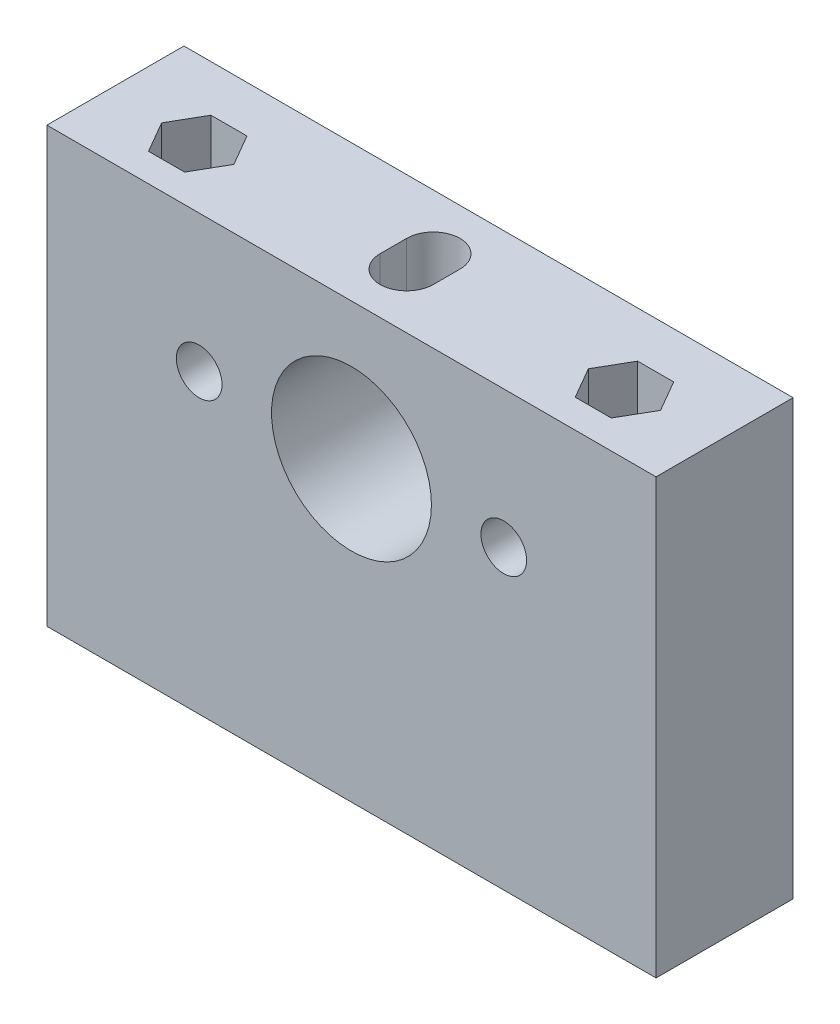
SolidWorks part; units mm, degrees
ref_plane "Front Plane" through (0, 0, 0) normal (0, 0, 1) x (1, 0, 0)
ref_plane "Top Plane" through (0, 0, 0) normal (0, 1, 0) x (1, 0, 0)
ref_plane "Right Plane" through (0, 0, 0) normal (1, 0, 0) x (0, 0, -1)
sketch "Sketch1" plane through (0, 0, 0) normal (0, 1, 0) x (1, 0, 0)
  line L0 (147.5033, 0) -> (147.5033, -18)
  line L1 (0, 0) -> (215, 0)
  line L2 (0, 0) -> (0, -18)
  line L3 (0, -18) -> (215, -18)
  line L4 (215, 0) -> (215, -18)
  line L5 (67.5033, 0) -> (67.5033, -18)
  line L6 (104.0033, -10.75) -> (104.0033, -7.25)
  line L7 (111.0033, -10.75) -> (111.0033, -7.25)
  line L8 (95.0033, -18) -> (95.0033, 0)
  line L9 (120.0033, -18) -> (120.0033, 0)
  line L10 (137.8704, -6.05) -> (133.1362, -6.05)
  line L11 (133.1362, -6.05) -> (130.769, -10.15)
  line L12 (130.769, -10.15) -> (133.1362, -14.25)
  line L13 (133.1362, -14.25) -> (137.8704, -14.25)
  line L14 (137.8704, -14.25) -> (140.2376, -10.15)
  line L15 (140.2376, -10.15) -> (137.8704, -6.05)
  line L16 (137.8704, -6.05) -> (133.1362, -14.25) construction
  line L17 (133.1362, -6.05) -> (137.8704, -14.25) construction
  line L18 (107.5, 0) -> (107.5033, -3.75) construction
  line L19 (77.1547, -14.3034) -> (74.7803, -10.2076)
  line L20 (81.889, -14.2951) -> (77.1547, -14.3034)
  line L21 (84.2489, -10.1909) -> (81.889, -14.2951)
  line L22 (81.8745, -6.0951) -> (84.2489, -10.1909)
  line L23 (74.7803, -10.2076) -> (77.1403, -6.1034)
  line L24 (77.1403, -6.1034) -> (81.889, -14.2951) construction
  line L25 (81.8745, -6.0951) -> (77.1547, -14.3034) construction
  line L26 (77.1403, -6.1034) -> (81.8745, -6.0951)
  circle A0 centre (9.99, -11.15) radius 3
  circle A1 centre (41.99, -11.15) radius 3
  circle A2 centre (79.5033, -10.15) radius 3
  circle A3 centre (135.5033, -10.15) radius 3
  circle A4 centre (173.0133, -11.15) radius 3
  circle A5 centre (205.0133, -11.15) radius 3
  circle A6 centre (107.5033, -10.75) radius 3.5
  circle A7 centre (107.5033, -7.25) radius 3.5
  point P39 (135.5033, -10.15)
  point P52 (145.2133, -3.97)
  point P53 (140.4635, -3.97)
  dimension "D5" = 6
  dimension "D6" = 6
  dimension "D16" = 7
  dimension "D1" = 215
  dimension "D2" = 18
  dimension "D3" = 11.15
  dimension "D7" = 32
  dimension "D8" = 56
  dimension "D9" = 32
  dimension "D10" = 37.5133
  dimension "D11" = 37.51
  dimension "D12" = 9.99
  dimension "D13" = 9.9867
  dimension "D14" = 80
  dimension "D15" = 12
  dimension "D4" = 10.15
  dimension "D17" = 40
  dimension "D18" = 7.25
  dimension "D19" = 25
  dimension "D20" = 15.5
  dimension "D21" = 8.2
  dimension "D22" = 8.2
  dimension "D23" = 8.2
  dimension "D28" = 2.29
  dimension "D29" = 4.7498
  dimension "D31" = 3.97
extrude "Boss-Extrude1" add sketch "Sketch1" along normal blind 20 contours L1 L5 L3 L0 A7 L7 A6 L6 A3 A2 | A7 A6 | A6 A7 | A6 A7 | A7 A6 L7 | A7 L6 A6 | L3 L8 L1 L5 A2 | L9 L3 L0 L1 A3 | L14 L15 L10 L11 L12 L13 A3 | L26 L23 L19 L20 L21 L22 A2 | L10 L15 region at (147.1746, 0, 9) region at (119.6952, 0, 9) region at (94.6746, 0, 9) region at (107.5033, 0, 11.8736) region at (104.1422, 0, 9) region at (107.5033, 0, 6.1264) region at (110.8644, 0, 9) region at (107.5033, 0, 9) region at (138.9455, 0, 8.1626) region at (76.0759, 0, 12.1927)
extrude "Boss-Extrude2" add sketch "Sketch1<3>" along normal blind 47 contours L0 L1 L9 L3 L15 L14 L13 L12 L11 L10 | L3 L8 L1 L5 L23 L26 L22 L21 L20 L19 | L3 L9 L1 L8 A7 L7 A6 L6 | A6 A7 | A7 A6 | A7 L6 A6 | A7 A6 L7 | A6 A7 region at (147.1746, 0, 9) region at (119.6952, 0, 9) region at (94.6746, 0, 9) region at (107.5033, 0, 11.8736) region at (104.1422, 0, 9) region at (107.5033, 0, 6.1264) region at (110.8644, 0, 9) region at (107.5033, 0, 9)
sketch "Sketch1<3>" plane through (0, 0, 0) normal (0, 1, 0) x (1, 0, 0) same geometry as "Sketch1"
ref_plane "Plane1" through (0, 0, 18) normal (0, 0, 1) x (1, 0, 0)
sketch "Sketch2" plane through (0, 0, 18) normal (0, 0, 1) x (1, 0, 0)
  line L0 (147.5033, 47) -> (147.5033, 0) construction
  line L1 (67.5033, 47) -> (147.5033, 47) construction
  line L2 (67.5033, 47) -> (67.5033, 0) construction
  line L3 (140.1533, 31) -> (130.8533, 31)
  line L4 (140.1533, 31) -> (140.1533, 26)
  line L5 (140.1533, 26) -> (130.8533, 26)
  line L6 (130.8533, 31) -> (130.8533, 26)
  line L7 (84.1533, 31) -> (74.8533, 31)
  line L8 (84.1533, 31) -> (84.1533, 26)
  line L9 (84.1533, 26) -> (74.8533, 26)
  line L10 (74.8533, 31) -> (74.8533, 26)
  circle A0 centre (127.5033, 38.99) radius 3
  circle A1 centre (87.5033, 38.99) radius 3
  circle A2 centre (107.5033, 39.05) radius 10.5
  circle A3 centre (87.5033, 38.99) radius 4.475
  circle A4 centre (127.5033, 38.99) radius 4.475
  circle A5 centre (127.5033, 38.99) radius 5.5
  circle A6 centre (87.5033, 38.99) radius 5.5
  dimension "D1" = 6
  dimension "D11" = 21
  dimension "D14" = 8.95
  dimension "D15" = 11
  dimension "D2" = 40
  dimension "D3" = 20
  dimension "D4" = 8.01
  dimension "D5" = 9.3
  dimension "D6" = 5
  dimension "D7" = 7.35
  dimension "D8" = 7.35
  dimension "D9" = 16
  dimension "D10" = 40
  dimension "D12" = 7.95
  dimension "D13" = 0.06
extrude "Boss-Extrude3" add sketch "Sketch1<6>" along normal blind 10 from surface contours L3 L9 L1 L8 A7 L7 A6 L6 | L3 L8 L1 L5 A2 | L9 L3 L0 L1 A3 region at (147.1746, 0, 9) region at (119.6952, 0, 9) region at (94.6746, 0, 9) starting at face at (135.5033, 47, 10.15)
sketch "Sketch1<6>" plane through (0, 0, 0) normal (0, 1, 0) x (1, 0, 0) same geometry as "Sketch1"
extrude "Boss-Extrude4" add sketch "Sketch2" against normal blind 25 contours A3 A1 | A4 A0 | A6 A3 | A5 A4 region at (83.1549, 38.99, 18) region at (123.1549, 38.99, 18) region at (122.1589, 38.99, 18) region at (82.1589, 38.99, 18)
extrude "Cut-Extrude5" cut sketch "Sketch2<6>" against normal through all contours A2 | A1 | A0 region at (127.5033, 38.99, 18) region at (87.5033, 38.99, 18) region at (107.5033, 39.05, 18)
sketch "Sketch2<6>" plane through (0, 0, 18) normal (0, 0, 1) x (1, 0, 0) same geometry as "Sketch2"
extrude "Cut-Extrude6" cut sketch "Sketch1<8>" along normal up to surface (57 mm away) contours A3 | A2 region at (79.5033, 0, 10.15) region at (135.5033, 0, 10.15) up to face at (107.5033, 57, 9)
sketch "Sketch1<8>" plane through (0, 0, 0) normal (0, 1, 0) x (1, 0, 0) same geometry as "Sketch1"
extrude "Cut-Extrude13" cut sketch "Sketch1<12>" against normal blind 30 from surface contours L14 L15 L10 L11 L12 L13 A3 | L26 L23 L19 L20 L21 L22 A2 region at (138.9455, 0, 8.1626) region at (76.0759, 0, 12.1927) starting at face at (107.5033, 57, 9)
sketch "Sketch1<12>" plane through (0, 0, 0) normal (0, 1, 0) x (1, 0, 0) same geometry as "Sketch1"
extrude "Cut-Extrude14" cut sketch "Sketch2<7>" along normal blind 10 from surface contours L7 L10 L9 L8 | L3 L6 L5 L4 region at (135.5033, 28.5, 18) region at (79.5033, 28.5, 18) starting at face at (97.0033, 39.05, 0)
sketch "Sketch2<7>" plane through (0, 0, 18) normal (0, 0, 1) x (1, 0, 0) same geometry as "Sketch2"
equation "\"D4@Sketch1\"=\"D3@Sketch1\"-1"
equation "\"D3@Sketch2\"=80/4"
equation "\"D7@Sketch2\"=12-(\"D5@Sketch2\"/2)"
equation "\"D8@Sketch2\"=12-(\"D5@Sketch2\"/2)"
equation "\"D18@Sketch1\"=(\"D2@Sketch1\"-(\"D16@Sketch1\"/2))/2"
equation "\"D20@Sketch1\"=(\"D8@Sketch1\"-\"D19@Sketch1\")/2"
equation "\"D21@Sketch1\"=\"D23@Sketch1\""
equation "\"D22@Sketch1\"=\"D23@Sketch1\""
